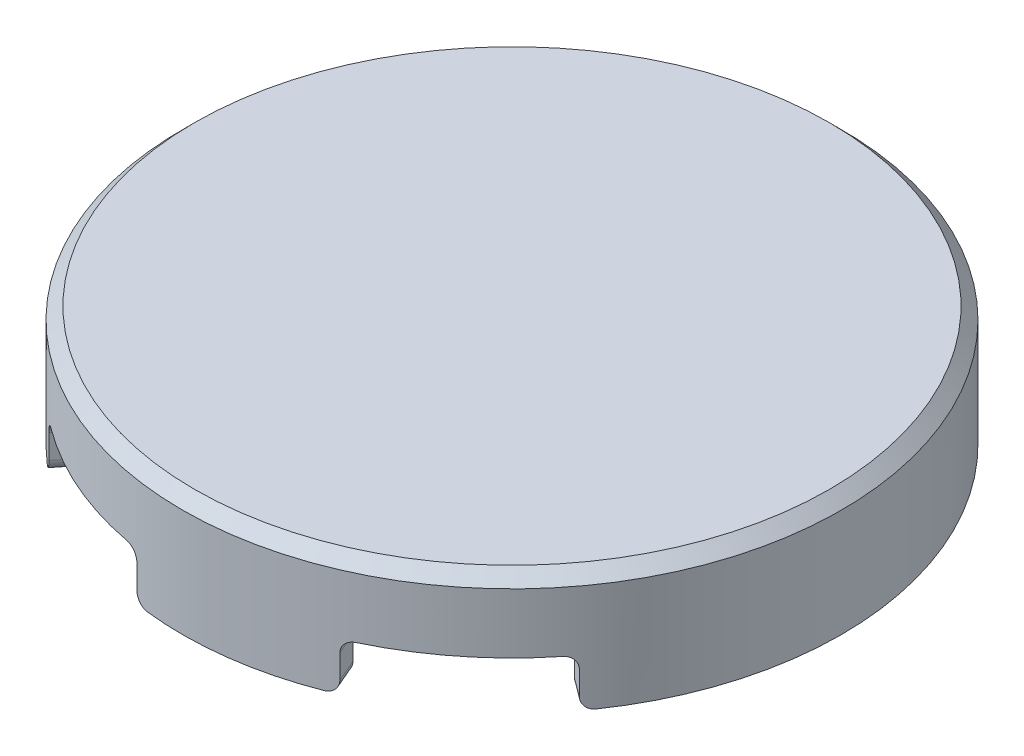
SolidWorks part; units mm, degrees
ref_plane "Front Plane" through (0, 0, 0) normal (0, 0, 1) x (1, 0, 0)
ref_plane "Top Plane" through (0, 0, 0) normal (0, 1, 0) x (1, 0, 0)
ref_plane "Right Plane" through (0, 0, 0) normal (1, 0, 0) x (0, 0, -1)
sketch "Sketch1" plane through (0, 0, 0) normal (0, 1, 0) x (1, 0, 0)
  circle A0 centre (0, 0) radius 13.75
  dimension "D1" = 27.5
extrude "Boss-Extrude1" add sketch "Sketch1" along normal blind 5
sketch "Sketch2" plane through (0, 0, 0) normal (0, -1, 0) x (1, 0, 0)
  circle A0 centre (0, 0) radius 12.7
  dimension "D1" = 25.4
extrude "Cut-Extrude1" cut sketch "Sketch2" against normal blind 3
chamfer "Chamfer1" distance 0.5 angle 45 1 edges at (0, 5, 13.75)
sketch "Sketch3" plane through (0, 5, 0) normal (0, 1, 0) x (1, 0, 0)
  point P0 (4.9777, 49.6482)
  point P1 (4.9777, 49.6482)
  point P2 (0, 0)
sketch_block_instance "Block1-2"
sketch_block "Block1"
ref_plane "Plane1" through (13.75, 0, 0) normal (1, 0, 0) x (0, 0, -1)
ref_plane "Plane2" through (0, 0, 13.75) normal (0, 0, 1) x (1, 0, 0)
ref_axis "Axis1" through (13.75, 8.7042, 13.75) along (0, -1, 0)
ref_point "Point1"
ref_point "Point2"
sketch "Sketch4" plane through (0, 0, 0) normal (0, -1, 0) x (1, 0, 0)
  line L0 (0, 0) -> (5.8385, -13.3571) construction
  line L1 (0, 0) -> (8.5803, -10.7443)
  line L2 (0, 0) -> (2.0586, -13.595)
  line L3 (0, 0) -> (-1.9198, -14.8766) construction
  line L4 (0, 0) -> (-13.6369, 1.7598) construction
  line L5 (0, 0) -> (-5.4425, -12.627)
  line L6 (0, 0) -> (-11.0269, -8.2141)
  line L7 (-11.4233, -10.3867) -> (-11.6456, -12.1091)
  line L8 (-8.1899, 14.6689) -> (-8.4122, 12.9464)
  line L9 (10.3499, 13.7887) -> (-6.5103, 15.9645)
  line L10 (11.4233, 10.3867) -> (11.6456, 12.1091)
  line L11 (8.1899, -14.6689) -> (8.4122, -12.9464)
  line L12 (-10.3499, -13.7887) -> (6.5103, -15.9645)
  line L13 (-11.4233, -10.3867) -> (-11.6456, -12.1091)
  line L14 (-8.1899, 14.6689) -> (-8.4122, 12.9464)
  line L15 (10.3499, 13.7887) -> (-6.5103, 15.9645)
  line L16 (11.4233, 10.3867) -> (11.6456, 12.1091)
  line L17 (8.1899, -14.6689) -> (8.4122, -12.9464)
  line L18 (-10.3499, -13.7887) -> (6.5103, -15.9645)
  line L19 (0, 0) -> (-8.5803, 10.7443)
  line L20 (0, 0) -> (-2.0586, 13.595)
  line L21 (0, 0) -> (5.4425, 12.627)
  line L22 (0, 0) -> (11.0269, 8.2141)
  circle A0 centre (5.8385, -13.3571) radius 1.025 construction
  circle A1 centre (0, 0) radius 13.75
  circle A2 centre (0, 0) radius 13.75
  circle A3 centre (-9.0382, -11.4373) radius 1.025 construction
  circle A4 centre (9.0382, 11.4373) radius 1.025 construction
  circle A5 centre (-5.8385, 13.3571) radius 1.025 construction
  circle A6 centre (5.8385, -13.3571) radius 1.025 construction
  circle A7 centre (-9.0382, -11.4373) radius 1.025 construction
  circle A8 centre (9.0382, 11.4373) radius 1.025 construction
  circle A9 centre (-5.8385, 13.3571) radius 1.025 construction
  circle A10 centre (0, 0) radius 12.7 construction
  circle A11 centre (0, 0) radius 12.7
  arc A12 (-11.4233, -10.3867) -> (-11.9477, -8.216) centre (-14.5226, -9.9867) ccw
  arc A13 (-9.4704, 10.98) -> (-11.9477, -8.216) centre (0, 0) ccw
  arc A14 (-9.4704, 10.98) -> (-8.4122, 12.9464) centre (-11.5115, 13.3464) ccw
  arc A15 (-6.5103, 15.9645) -> (-8.1899, 14.6689) centre (-6.7023, 14.4769) ccw
  arc A16 (11.6456, 12.1091) -> (10.3499, 13.7887) centre (10.1579, 12.3011) ccw
  arc A17 (11.4233, 10.3867) -> (11.9477, 8.216) centre (14.5226, 9.9867) ccw
  arc A18 (9.4704, -10.98) -> (11.9477, 8.216) centre (0, 0) ccw
  arc A19 (9.4704, -10.98) -> (8.4122, -12.9464) centre (11.5115, -13.3464) ccw
  arc A20 (6.5103, -15.9645) -> (8.1899, -14.6689) centre (6.7023, -14.4769) ccw
  arc A21 (-11.6456, -12.1091) -> (-10.3499, -13.7887) centre (-10.1579, -12.3011) ccw
  arc A22 (-11.4233, -10.3867) -> (-11.9477, -8.216) centre (-14.5226, -9.9867) ccw
  arc A23 (-9.4704, 10.98) -> (-11.9477, -8.216) centre (0, 0) ccw
  arc A24 (-9.4704, 10.98) -> (-8.4122, 12.9464) centre (-11.5115, 13.3464) ccw
  arc A25 (-6.5103, 15.9645) -> (-8.1899, 14.6689) centre (-6.7023, 14.4769) ccw
  arc A26 (11.6456, 12.1091) -> (10.3499, 13.7887) centre (10.1579, 12.3011) ccw
  arc A27 (11.4233, 10.3867) -> (11.9477, 8.216) centre (14.5226, 9.9867) ccw
  arc A28 (9.4704, -10.98) -> (11.9477, 8.216) centre (0, 0) ccw
  arc A29 (9.4704, -10.98) -> (8.4122, -12.9464) centre (11.5115, -13.3464) ccw
  arc A30 (6.5103, -15.9645) -> (8.1899, -14.6689) centre (6.7023, -14.4769) ccw
  arc A31 (-11.6456, -12.1091) -> (-10.3499, -13.7887) centre (-10.1579, -12.3011) ccw
  circle M26 centre (0, 0) radius 12.7
  circle M27 centre (0, 0) radius 13.75
  dimension "D3" = 15
  dimension "D1" = 0
  dimension "D2" = 0
extrude "Cut-Extrude2" cut sketch "Sketch4" against normal blind 2 contours A6 L1 L2 M27 M26 | A7 L5 L6 M27 M26 | A9 L19 L20 M27 M26 | A8 L21 L22 M27 M26 region at (5.2393, 0, -11.9863) region at (-8.1106, 0, -10.2635) region at (-5.2393, 0, 11.9863) region at (8.1106, 0, 10.2635)
fillet "Fillet1" radius 0.5 16 edges at (5.2347, 2, 12.1449) (5.2347, 0, 12.1449) (10.6058, 0, 7.9004) (10.6058, 2, 7.9004) (-1.98, 2, 13.0759) (-1.98, 0, 13.0759) (-8.2527, 2, 10.3341) (-8.2527, 0, 10.3341) (-10.6058, 0, -7.9004) (-10.6058, 2, -7.9004) (-5.2347, 2, -12.1449) (-5.2347, 0, -12.1449) (1.98, 0, -13.0759) (1.98, 2, -13.0759) (8.2527, 0, -10.3341) (8.2527, 2, -10.3341)
